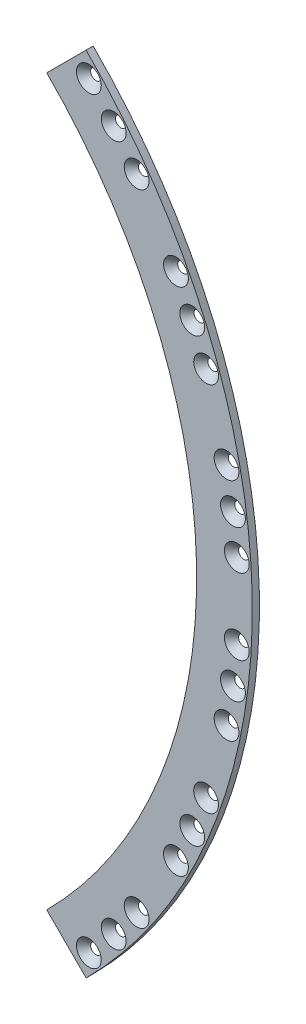
SolidWorks part; units mm, degrees
ref_plane "Front Plane" through (0, 0, 0) normal (0, 0, 1) x (1, 0, 0)
ref_plane "Top Plane" through (0, 0, 0) normal (0, 1, 0) x (1, 0, 0)
ref_plane "Right Plane" through (0, 0, 0) normal (1, 0, 0) x (0, 0, -1)
sketch "Sketch1" plane through (0, 0, 0) normal (0, 0, 1) x (1, 0, 0)
  line L0 (0, 0) -> (113.4199, -113.4199) construction
  line L1 (0, 0) -> (113.4199, 113.4199) construction
  line L2 (160.4, 0) -> (147.4, 0) construction
  line L3 (102.3184, 102.3184) -> (113.4199, 113.4199)
  line L4 (102.3184, -102.3184) -> (113.4199, -113.4199)
  line L5 (153.1288, 31.8205) -> (154.9433, 21.2965) construction
  line L6 (154.9433, 21.2965) -> (156.0354, 10.6731) construction
  line L7 (143.4518, 62.3099) -> (138.8652, 71.9542) construction
  line L8 (138.8652, 71.9542) -> (121.3212, 98.7022) construction
  line L9 (121.3212, 98.7022) -> (114.3027, 106.7513) construction
  line L10 (114.3027, 106.7513) -> (114.3027, -106.7513) construction
  line L11 (114.3027, -106.7513) -> (121.3212, -98.7022) construction
  line L12 (121.3212, -98.7022) -> (138.8652, -71.9542) construction
  line L13 (138.8652, -71.9542) -> (143.4518, -62.3099) construction
  arc A0 (0, -160.4) -> (0, 160.4) centre (0, 0) ccw construction
  circle A1 centre (121.3212, 98.7022) radius 1.5
  circle A2 centre (143.4518, 62.3099) radius 1.5
  circle A3 centre (154.9433, 21.2965) radius 1.5
  circle A4 centre (154.9433, -21.2965) radius 1.5
  circle A5 centre (143.4518, -62.3099) radius 1.5
  circle A6 centre (121.3212, -98.7022) radius 1.5
  circle A7 centre (10.6731, -156.0354) radius 1.5 construction
  circle A8 centre (31.8205, -153.1288) radius 1.5 construction
  circle A9 centre (52.3752, -147.3696) radius 1.5 construction
  circle A10 centre (90.1928, -127.7741) radius 1.5 construction
  circle A11 centre (10.6731, 156.0354) radius 1.5 construction
  circle A12 centre (31.8205, 153.1288) radius 1.5 construction
  circle A13 centre (52.3752, 147.3696) radius 1.5 construction
  circle A14 centre (90.1928, 127.7741) radius 1.5 construction
  circle A16 centre (127.7741, 90.1928) radius 1.5
  circle A17 centre (147.3696, 52.3752) radius 1.5
  circle A18 centre (153.1288, 31.8205) radius 1.5
  circle A19 centre (156.0354, 10.6731) radius 1.5
  circle A20 centre (127.7741, -90.1928) radius 1.5
  circle A21 centre (147.3696, -52.3752) radius 1.5
  circle A22 centre (153.1288, -31.8205) radius 1.5
  circle A23 centre (156.0354, -10.6731) radius 1.5
  arc A24 (113.4199, 113.4199) -> (113.4199, -113.4199) centre (0, 0) cw
  arc A25 (102.3184, 102.3184) -> (102.3184, -102.3184) centre (0, 0) cw
  arc A26 (144.6991, 0.5) -> (-144.6991, 0.5) centre (0, 0) ccw construction
  arc A27 (-144.6991, -0.5) -> (144.6991, -0.5) centre (0, 0) ccw construction
  arc A28 (110.5915, 110.5915) -> (110.5915, -110.5915) centre (0, 0) cw construction
  circle A29 centre (138.8652, 71.9542) radius 1.5
  circle A30 centre (114.3027, 106.7513) radius 1.5
  circle A31 centre (138.8652, -71.9542) radius 1.5
  circle A32 centre (114.3027, -106.7513) radius 1.5
  dimension "D3" = 3
  dimension "D1" = 45
  dimension "D2" = 45
extrude "Boss-Extrude1" add sketch "Sketch1" along normal blind 2
sketch "Sketch2" plane through (0, 0, 2) normal (0, 0, 1) x (1, 0, 0)
  line L0 (117.1059, 116.8938) -> (92.6963, 92.4842)
  line L1 (117.1059, 116.8938) -> (106.0237, 127.976)
  line L2 (92.6963, 92.4842) -> (81.6141, 103.5664)
  line L3 (106.0237, 127.976) -> (81.6141, 103.5664)
  line L4 (94.9531, -94.741) -> (127.5884, -127.3763)
  line L5 (94.9531, -94.741) -> (73.4751, -116.219)
  line L6 (127.5884, -127.3763) -> (106.1104, -148.8543)
  line L7 (73.4751, -116.219) -> (106.1104, -148.8543)
  line L8 (113.4199, 113.4199) -> (102.3184, 102.3184) construction
  line L9 (102.3184, -102.3184) -> (113.4199, -113.4199) construction
  dimension "D1" = 0.15
  dimension "D2" = 0.15
extrude "Cut-Extrude1" cut sketch "Sketch2" against normal through all
chamfer "Chamfer1" distance 2 angle 45 18 edges at (115.8027, -106.7513, 2) (122.8212, -98.7022, 2) (126.2741, -90.1928, 2) (140.3652, -71.9542, 2) (144.9518, -62.3099, 2) (145.8696, -52.3752, 2) (151.6288, -31.8205, 2) (156.4433, -21.2965, 2) (154.5354, -10.6731, 2) (154.5354, 10.6731, 2) (156.4433, 21.2965, 2) (151.6288, 31.8205, 2) (145.8696, 52.3752, 2) (144.9518, 62.3099, 2) (140.3652, 71.9542, 2) (126.2741, 90.1928, 2) (122.8212, 98.7022, 2) (115.8027, 106.7513, 2)
